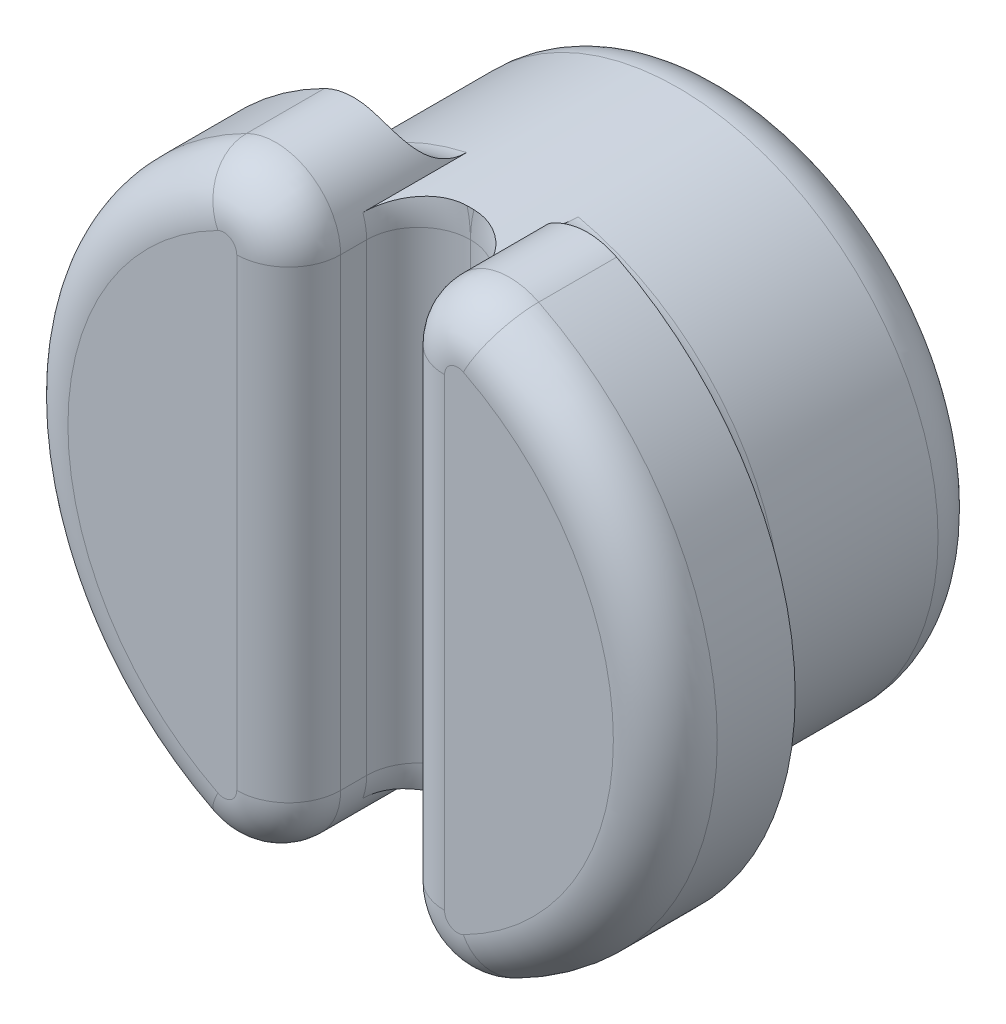
SolidWorks part; units mm, degrees
material "PVC rigide"
ref_plane "Plan de face" through (0, 0, 0) normal (0, 0, 1) x (1, 0, 0)
ref_plane "Plan de dessus" through (0, 0, 0) normal (0, 1, 0) x (1, 0, 0)
ref_plane "Plan de droite" through (0, 0, 0) normal (1, 0, 0) x (0, 0, -1)
sketch "Esquisse1" plane through (0, 0, 0) normal (0, 0, 1) x (1, 0, 0)
  circle A0 centre (0, 0) radius 2
  dimension "D1" = 4
extrude "Boss.-Extru.1" add sketch "Esquisse1" along normal blind 2
sketch "Esquisse2" plane through (0, 0, 2) normal (0, 0, 1) x (1, 0, 0)
  line L0 (0.4, 1.7861) -> (0.4, -1.7861)
  arc A0 (1.125, -2.2326) -> (1.125, 2.2326) centre (0, 0) ccw
  arc A1 (0.4, 1.7861) -> (1.125, 2.2326) centre (0.9, 1.7861) cw
  arc A2 (0.4, -1.7861) -> (1.125, -2.2326) centre (0.9, -1.7861) ccw
  dimension "D1" = 5
  dimension "D3" = 0.5
  dimension "D2" = 0.4
extrude "Boss.-Extru.2" add sketch "Esquisse2" along normal blind 1
sketch "Esquisse3" plane through (0, 0, 2) normal (0, 0, 1) x (1, 0, 0)
  line L0 (-0.4, 1.7861) -> (-0.4, -1.7861)
  arc A0 (-1.125, 2.2326) -> (-1.125, -2.2326) centre (0, 0) ccw
  arc A1 (-0.4, -1.7861) -> (-1.125, -2.2326) centre (-0.9, -1.7861) cw
  arc A2 (-0.4, 1.7861) -> (-1.125, 2.2326) centre (-0.9, 1.7861) ccw
  dimension "D2" = 5
  dimension "D3" = 0.5
  dimension "D1" = 0.4
extrude "Boss.-Extru.3" add sketch "Esquisse3" along normal blind 1
fillet "Congé1" radius 0.4 14 edges at (0.4073, 1.871, 2) (0.4073, -1.871, 2) (-0.4073, -1.871, 2) (-0.4073, 1.871, 2) (2.5, 0, 3) (0.6378, -2.2118, 3) (0.4, 0, 3) (0.6378, 2.2118, 3) (-2.5, 0, 3) (-0.6378, 2.2118, 3) (-0.4, 0, 3) (-0.6378, -2.2118, 3) (0.4, 0, 2) (-0.4, 0, 2)
fillet "Congé2" radius 0.4 3 edges at (-2, 0, 2) (2, 0, 0) (2, 0, 2)
